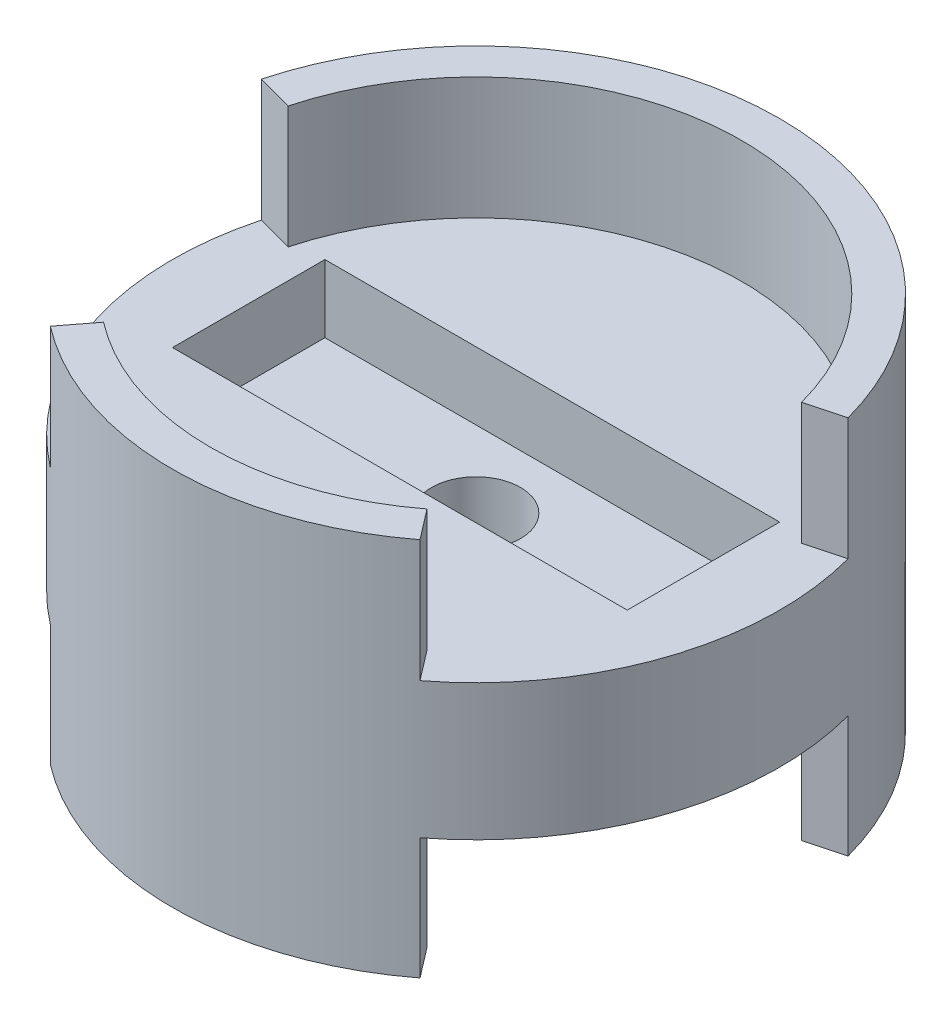
SolidWorks part; units mm, degrees
ref_plane "Front Plane" through (0, 0, 0) normal (0, 0, 1) x (1, 0, 0)
ref_plane "Top Plane" through (0, 0, 0) normal (0, 1, 0) x (1, 0, 0)
ref_plane "Right Plane" through (0, 0, 0) normal (1, 0, 0) x (0, 0, -1)
sketch "Sketch1" plane through (0, 0, 0) normal (0, 1, 0) x (1, 0, 0)
  line L1 (19.0182, -6.3754) -> (-19.0183, -6.3754)
  line L2 (19.0182, -6.3754) -> (19.0182, 6.3754)
  line L3 (19.0182, 6.3754) -> (-19.0183, 6.3754)
  line L4 (-19.0183, -6.3754) -> (-19.0183, 6.3754)
  line L5 (19.0182, -6.3754) -> (-19.0183, 6.3754) construction
  line L6 (19.0182, 6.3754) -> (-19.0183, -6.3754) construction
  circle A0 centre (0, 0) radius 25.4
  circle A1 centre (0, 0) radius 3.7147
  dimension "D1" = 50.8
  dimension "D4" = 7.4295
  dimension "D2" = 38.0365
  dimension "D3" = 12.7508
extrude "Boss-Extrude1" add sketch "Sketch1" along normal blind 5.6642 contours A0 L1 L4 L3 L2 region at (-24.6816, 0, 0)
extrude "Boss-Extrude2" add sketch "Sketch1<3>" against normal blind 5.715 contours A0 L1 L4 L3 L2 | L4 L1 L2 L3 A1 region at (0, 0, 5.9742) region at (-24.6816, 0, 0)
sketch "Sketch1<3>" plane through (0, 0, 0) normal (0, 1, 0) x (1, 0, 0) same geometry as "Sketch1"
sketch "Sketch2" plane through (0, 0, 0) normal (0, 1, 0) x (1, 0, 0)
  line L5 (21.4677, 5.7523) -> (24.5345, 6.574)
  line L6 (0, -25.4) -> (0, 25.4) construction
  line L7 (-21.4677, 5.7523) -> (-24.5345, 6.574)
  line L8 (-13.5297, -17.6323) -> (-15.4625, -20.1512)
  line L9 (13.5297, -17.6323) -> (15.4625, -20.1512)
  arc A4 (-15.4625, -20.1512) -> (15.4625, -20.1512) centre (0, 0) ccw
  arc A5 (-13.5297, -17.6323) -> (13.5297, -17.6323) centre (0, 0) ccw
  arc A6 (21.4677, 5.7523) -> (-21.4677, 5.7523) centre (0, 0) ccw
  arc A7 (24.5345, 6.574) -> (-24.5345, 6.574) centre (0, 0) ccw
  point P7 (0, 0)
  point P10 (0, 0)
  point P13 (0, 0)
  dimension "D1" = 50.8
  dimension "D2" = 44.45
  dimension "D3" = 75
  dimension "D4" = 75
  dimension "D5" = 75
  dimension "D6" = 27.0594
  dimension "D7" = 5.7523
  dimension "D8" = 5.7523
extrude "Boss-Extrude3" add sketch "Sketch2" along normal mid plane 31.75 contours L7 A7 L5 A6 | L8 A4 L9 A5
